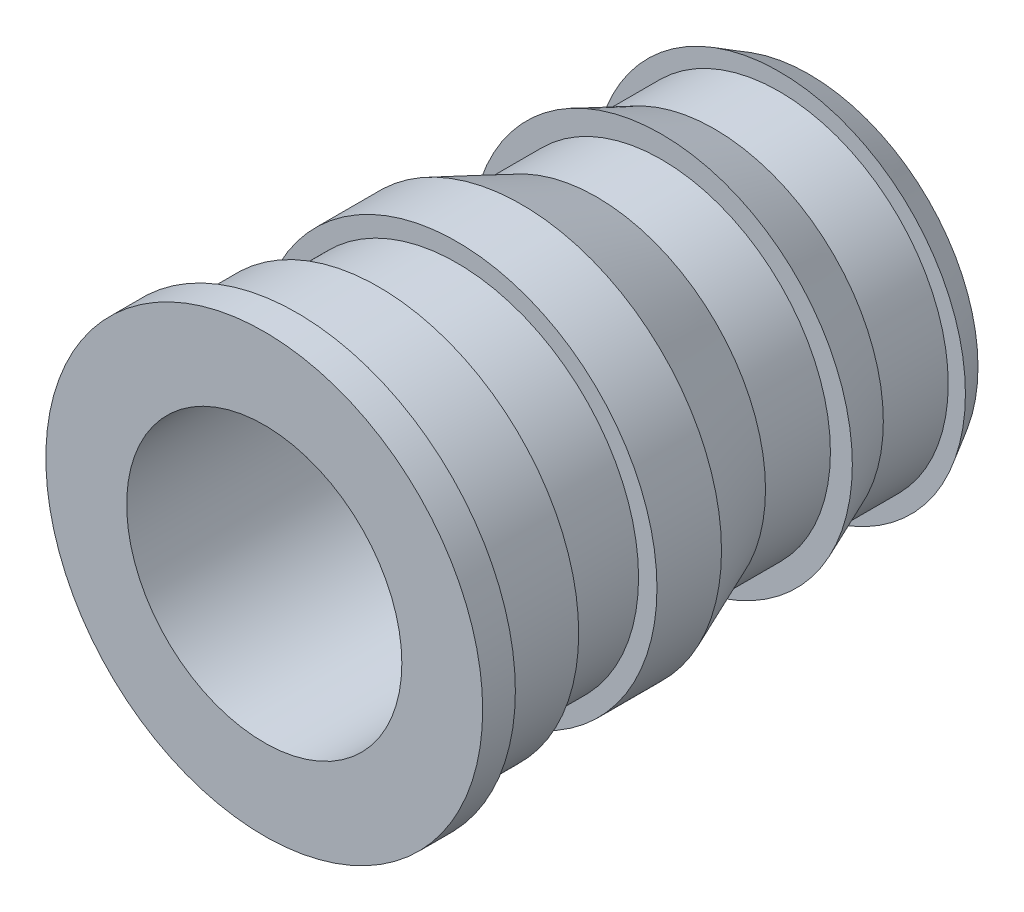
SolidWorks part; units mm, degrees
material "Brass"
ref_plane "Front Plane" through (0, 0, 0) normal (0, 0, 1) x (1, 0, 0)
ref_plane "Top Plane" through (0, 0, 0) normal (0, 1, 0) x (1, 0, 0)
ref_plane "Right Plane" through (0, 0, 0) normal (1, 0, 0) x (0, 0, -1)
sketch "Sketch1" plane through (0, 0, 0) normal (1, 0, 0) x (0, 0, -1)
  line L0 (-3.96, 0) -> (3.96, 0) construction
  line L1 (-3.96, 2) -> (-3.96, 3.175)
  line L2 (-3.96, 3.175) -> (-3.4848, 3.175)
  line L3 (-3.4848, 3.175) -> (-3.4848, 2.9075)
  line L4 (-3.4848, 2.9075) -> (-2.2968, 2.9075)
  line L5 (-2.2968, 2.9075) -> (-2.2968, 2.64)
  line L6 (-2.2968, 2.64) -> (-1.1589, 2.64)
  line L7 (-1.1589, 2.64) -> (-1.1589, 2.9075)
  line L9 (-0.2207, 2.9075) -> (0.8712, 2.4552)
  line L10 (1.8147, 2.7737) -> (1.8147, 2.4552)
  line L11 (1.8147, 2.4552) -> (0.8712, 2.4552)
  line L12 (1.8147, 2.7737) -> (2.5838, 2.4552)
  line L13 (2.5838, 2.4552) -> (3.5273, 2.4552)
  line L14 (3.5273, 2.4552) -> (3.5273, 2.705)
  line L15 (3.5273, 2.705) -> (3.96, 2.4552)
  line L16 (3.96, 2.4552) -> (3.96, 2)
  line L17 (-3.96, 2.705) -> (3.96, 2.705) construction
  line L18 (3.96, 0) -> (3.96, 2.705) construction
  line L19 (-3.96, 0) -> (-3.96, 3.175) construction
  line L20 (-1.1589, 2.9075) -> (-0.2207, 2.9075)
  line L21 (-3.96, 2) -> (3.96, 2)
  line L22 (-3.96, -2.705) -> (3.96, -2.705) construction
  line L23 (-4.6163, 2.0758) -> (-4.2663, 1.4696) construction
  line L25 (-4.2663, 1.4696) -> (-3.9163, 2.0758) construction
  line L26 (-3.9163, 2.0758) -> (-4.6163, 2.0758) construction
  line L27 (-4.5725, 2) -> (-3.96, 2) construction
  line L28 (-4.2663, 2.0758) -> (-4.2663, 2) construction
  line L29 (-4.2663, 2) -> (-4.2663, 1.5453) construction
  line L30 (-4.2663, 1.5453) -> (-4.2663, 1.4696) construction
  line L31 (-4.31, 1.5453) -> (-4.2225, 1.5453)
  line L32 (-4.5944, 2.0379) -> (-3.9381, 2.0379)
  line L33 (-4.2225, 1.5453) -> (-3.9381, 2.0379)
  line L34 (-4.31, 1.5453) -> (-4.5944, 2.0379)
  line L35 (-3.96, 2.64) -> (3.96, 2.64) construction
  line L36 (-3.96, -2.64) -> (3.96, -2.64) construction
  point P27 (-1.1589, 2.7738)
  point P36 (-4.2663, 2.0379)
  point P41 (0.4251, 2.64)
  dimension "Installed Length" = 7.92
  dimension "Dia A" = 6.35
  dimension "Dia B" = 5.41
  dimension "Thread Dia" = 4
  dimension "D6" = 30
  dimension "D8" = 1.188
  dimension "D4" = 22.5
  dimension "Thread Pitch" = 0.7
  dimension "D2" = 0.0875
  dimension "Max Hole Dia" = 5.28
  dimension "D3" = 4.9104
  dimension "Knurling Length" = 4.356
  dimension "D1" = 0.4752
  dimension "D5" = 1.584
ref_plane "Plane1" through (0, 0, 3.4848) normal (0, 0, 1) x (1, 0, 0)
sketch "Sketch2" plane through (0, 0, 3.4848) normal (0, 0, 1) x (1, 0, 0)
  line L0 (0, 0) -> (0, 2.9075) construction
  line L1 (-0.2028, 2.9004) -> (0, 2.64)
  line L2 (0.2028, 2.9004) -> (0, 2.64)
  line L3 (-0.2028, 2.9004) -> (0, 0) construction
  line L4 (0.2028, 2.9004) -> (0, 0) construction
  line L5 (0, 0) -> (-0.3795, 2.8826) construction
  line L6 (0, 0) -> (0.3795, 2.8826) construction
  line L7 (0, 0) -> (2.0559, 2.0559) construction
  line L8 (0, 0) -> (0, -2.0758) construction
  line L9 (0, 0) -> (1.0379, -1.7977) construction
  circle A0 centre (0, 0) radius 2.64 construction
  circle A1 centre (0, 0) radius 2.9075 construction
  arc A2 (-0.2028, 2.9004) -> (0.2028, 2.9004) centre (0, 0) cw
  circle A3 centre (0, 0) radius 2.0758
  dimension "For Hole Taper Angle" = 8
  dimension "Pattern Angle" = 15
  dimension "Helix Angle" = 45
  dimension "D1" = 30
sketch "Sketch3" plane through (0, 0, 0) normal (1, 0, 0) x (0, 0, -1)
  line L0 (-3.96, 2) -> (-3.96, 3.175) construction
  line L1 (-3.96, 3.175) -> (-3.4848, 3.175) construction
  line L2 (-3.4848, 3.175) -> (-3.4848, 2.9075) construction
  line L3 (-3.4848, 2.9075) -> (-2.2968, 2.9075) construction
  line L4 (-2.2968, 2.9075) -> (-2.2968, 2.64) construction
  line L5 (-2.2968, 2.64) -> (-1.1589, 2.64) construction
  line L6 (-1.1589, 2.64) -> (-1.1589, 2.9075) construction
  line L8 (-0.2207, 2.9075) -> (0.8712, 2.4552) construction
  line L9 (1.8147, 2.4552) -> (0.8712, 2.4552) construction
  line L10 (1.8147, 2.7737) -> (1.8147, 2.4552) construction
  line L11 (1.8147, 2.7737) -> (2.5838, 2.4552) construction
  line L12 (2.5838, 2.4552) -> (3.5273, 2.4552) construction
  line L13 (3.5273, 2.4552) -> (3.5273, 2.705) construction
  line L14 (3.5273, 2.705) -> (3.96, 2.4552) construction
  line L15 (3.96, 2.4552) -> (3.96, 2) construction
  line L16 (-3.96, 2) -> (3.96, 2) construction
  line L17 (-3.96, 2) -> (-3.96, 3.175)
  line L18 (-3.96, 3.175) -> (-3.4848, 3.175)
  line L19 (-3.4848, 3.175) -> (-3.4848, 2.9075)
  line L20 (-3.4848, 2.9075) -> (-2.2968, 2.9075)
  line L21 (-2.2968, 2.9075) -> (-2.2968, 2.64)
  line L22 (-2.2968, 2.64) -> (-1.1589, 2.64)
  line L23 (-1.1589, 2.64) -> (-1.1589, 2.9075)
  line L25 (-0.2207, 2.9075) -> (0.8712, 2.4552)
  line L26 (1.8147, 2.4552) -> (0.8712, 2.4552)
  line L27 (1.8147, 2.7737) -> (1.8147, 2.4552)
  line L28 (1.8147, 2.7737) -> (2.5838, 2.4552)
  line L29 (2.5838, 2.4552) -> (3.5273, 2.4552)
  line L30 (3.5273, 2.4552) -> (3.5273, 2.705)
  line L31 (3.5273, 2.705) -> (3.96, 2.4552)
  line L32 (3.96, 2.4552) -> (3.96, 2)
  line L33 (-3.96, 2) -> (3.96, 2)
  line L34 (-1.1589, 2.9075) -> (-0.2207, 2.9075) construction
  line L35 (-1.1589, 2.9075) -> (-0.2207, 2.9075)
revolve "Revolve1" add sketch "Sketch3" angle 360 about L0
sketch "Sketch4" [suppressed] plane through (0, 0, 3.4848) normal (0, 0, 1) x (1, 0, 0)
  circle A2 centre (0, 0) radius 2.9075 construction
  circle A3 centre (0, 0) radius 2.9075
sketch "Sketch6" [suppressed] plane through (0, 0, 3.96) normal (0, 0, 1) x (1, 0, 0)
  circle A0 centre (0, 0) radius 2
curve "Helix/Spiral2" [suppressed] pitch 0.7 height 8.62 turns 12.3143
sketch "Sketch7" [suppressed] plane through (0, 0, 0) normal (1, 0, 0) x (0, 0, -1)
  line L0 (-4.31, 1.5453) -> (-4.2225, 1.5453) construction
  line L1 (-4.31, 1.5453) -> (-4.5944, 2.0379) construction
  line L2 (-4.5944, 2.0379) -> (-3.9381, 2.0379) construction
  line L3 (-4.2225, 1.5453) -> (-3.9381, 2.0379) construction
  line L4 (-4.31, 1.5453) -> (-4.2225, 1.5453)
  line L5 (-4.31, 1.5453) -> (-4.5944, 2.0379)
  line L6 (-4.5944, 2.0379) -> (-3.9381, 2.0379)
  line L7 (-4.2225, 1.5453) -> (-3.9381, 2.0379)
sweep "Sweep1" [suppressed] add profiles "Sketch7" path "Helix/Spiral2"
sketch "Sketch8" [suppressed] plane through (0, 0, 3.96) normal (0, 0, 1) x (1, 0, 0)
  circle A0 centre (0, 0) radius 2.0758
extrude "Cut-Extrude1" [suppressed] cut sketch "Sketch8" against normal through all draft 45 and the other way through all
mirror "Mirror1" [suppressed] about plane through (0, 0, 0) normal (0, 0, 1)
curve "Helix/Spiral1" [suppressed] pitch 34.848 height 4.356 turns 0.125
sketch "Sketch5" [suppressed] plane through (0, 0, 3.4848) normal (0, 0, 1) x (1, 0, 0)
  line L0 (-0.2028, 2.9004) -> (0, 2.64) construction
  line L1 (0.2028, 2.9004) -> (0, 2.64) construction
  line L2 (-0.2028, 2.9004) -> (0, 2.64)
  line L3 (0.2028, 2.9004) -> (0, 2.64)
  arc A0 (0.2028, 2.9004) -> (-0.2028, 2.9004) centre (0, 0) ccw construction
  arc A1 (0.2028, 2.9004) -> (-0.2028, 2.9004) centre (0, 0) ccw
sweep "Cut-Sweep1" [suppressed] cut profiles "Sketch5" path "Helix/Spiral1"
pattern_circular "CirPattern1" [suppressed] count 24 over 360 about axis through (0, 0, 3.96) along (0, 0, -1) of bodies 105
equation "\"D8@Sketch1\" = \"Installed Length@Sketch1\" * .15"
equation "\"D4@Helix/Spiral1\"=\"Knurling Length@Sketch1\"*(360/\"Helix Angle@Sketch2\")"
equation "\"D3@Helix/Spiral1\"=\"Knurling Length@Sketch1\""
equation "\"D1@CirPattern1\"=\"D3@CirPattern1\"/\"Pattern Angle@Sketch2\""
equation "\"D2@Sketch1\" = \"Thread Pitch@Sketch1\" / 8"
equation "\"D4@Helix/Spiral2\"=\"Thread Pitch@Sketch1\""
equation "\"D3@Helix/Spiral2\" = \"Installed Length@Sketch1\" + \"Thread Pitch@Sketch1\""
equation "\"D3@Sketch1\"=\"Max Hole Dia@Sketch1\"*.93"
equation "\"Knurling Length@Sketch1\"=\"Installed Length@Sketch1\" * .55"
equation "\"D1@Sketch1\"=\"Installed Length@Sketch1\"*.06"
equation "\"D5@Sketch1\"=\"Installed Length@Sketch1\"*.2"
